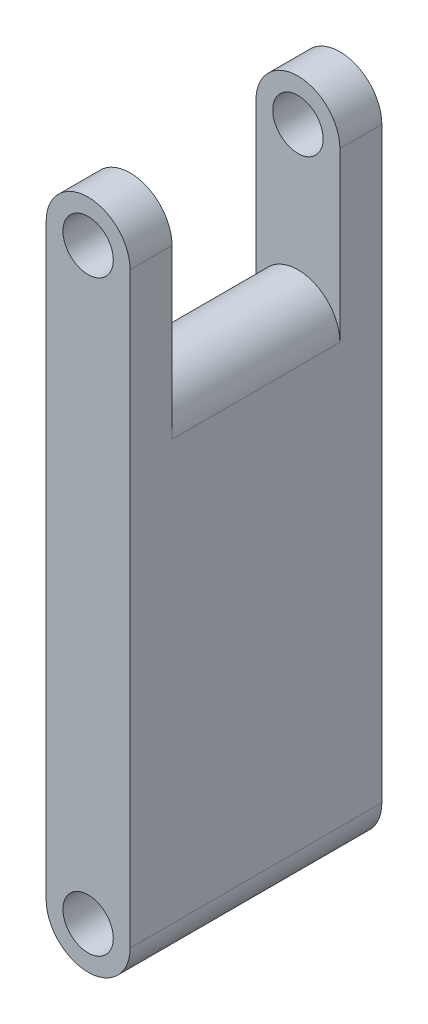
SolidWorks part; units mm, degrees
ref_plane "Front Plane" through (0, 0, 0) normal (0, 0, 1) x (1, 0, 0)
ref_plane "Top Plane" through (0, 0, 0) normal (0, 1, 0) x (1, 0, 0)
ref_plane "Right Plane" through (0, 0, 0) normal (1, 0, 0) x (0, 0, -1)
sketch "Sketch1" plane through (0, 0, 0) normal (0, 0, 1) x (1, 0, 0)
  line L1 (-6.35, 50.8) -> (6.35, 50.8)
  line L2 (-6.35, 50.8) -> (-6.35, -50.8)
  line L3 (-6.35, -50.8) -> (6.35, -50.8)
  line L4 (6.35, 50.8) -> (6.35, -50.8)
  line L5 (-6.35, 50.8) -> (6.35, -50.8) construction
  line L6 (-6.35, -50.8) -> (6.35, 50.8) construction
  point P0 (0, 0)
  dimension "D1" = 12.7
  dimension "D2" = 101.6
extrude "Boss-Extrude1" add sketch "Sketch1" along normal mid plane 38.1
fillet "Fillet2" 2 edges at (-6.35, -50.8, 0) (6.35, -50.8, 0) type full round first side face at (-6.35, 0, 0) second side face at (6.35, 0, 0) middle face at (0, -50.8, 0)
sketch "Sketch2" plane through (0, 0, 19.05) normal (0, 0, 1) x (1, 0, 0)
  circle A0 centre (0, -44.45) radius 3.81
  dimension "D1" = 7.62
extrude "Cut-Extrude1" cut sketch "Sketch2" against normal blind 38.1
mirror "Mirror3" about plane through (0, 0, 0) normal (0, 1, 0) of "Cut-Extrude1"
fillet "Fillet3" 2 edges at (-6.35, 50.8, 0) (6.35, 50.8, 0) type full round first side face at (-6.35, 3.175, 0) second side face at (6.35, 3.175, 0) middle face at (0, 50.8, 0)
sketch "Sketch3" plane through (-6.35, 0, 0) normal (-1, 0, 0) x (0, 0, 1)
  line L0 (-12.7, 50.8) -> (-12.7, 25.4)
  line L1 (19.05, 50.8) -> (-19.05, 50.8) construction
  line L2 (-12.7, 25.4) -> (12.7, 25.4)
  line L3 (12.7, 25.4) -> (12.7, 50.8)
  line L4 (12.7, 50.8) -> (-12.7, 50.8)
  line L5 (-19.05, 44.45) -> (-19.05, -44.45) construction
  line L6 (19.05, 44.45) -> (19.05, -44.45) construction
  dimension "D1" = 25.4
  dimension "D2" = 6.35
  dimension "D3" = 6.35
extrude "Cut-Extrude2" cut sketch "Sketch3" against normal through all
fillet "Fillet4" 2 edges at (-6.35, 25.4, 0) (6.35, 25.4, 0) type full round first side face at (-6.35, 17.4625, 0) second side face at (6.35, 17.4625, 0) middle face at (0, 25.4, 0)
